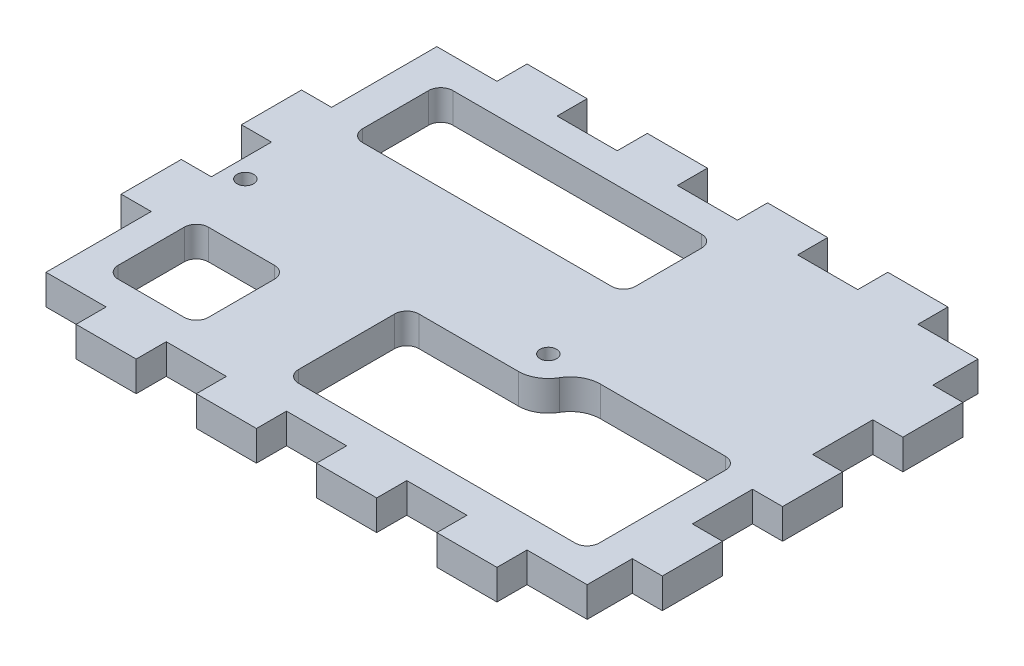
SolidWorks part; units mm, degrees
material "Pine"
ref_plane "Front Plane" through (0, 0, 0) normal (0, 0, 1) x (1, 0, 0)
ref_plane "Top Plane" through (0, 0, 0) normal (0, 1, 0) x (1, 0, 0)
ref_plane "Right Plane" through (0, 0, 0) normal (1, 0, 0) x (0, 0, -1)
sketch "Sketch1" plane through (0, 0, 0) normal (0, 1, 0) x (1, 0, 0)
  line L1 (0, 0) -> (431.8, 0)
  line L2 (0, 0) -> (0, 95.25)
  line L3 (0, 95.25) -> (431.8, 95.25)
  line L4 (431.8, 0) -> (431.8, 95.25)
  dimension "D1" = 431.8
  dimension "D2" = 95.25
extrude "Boss-Extrude1" add sketch "Sketch1" along normal blind 6.35
sketch "Sketch2" plane through (0, 6.35, 0) normal (0, 1, 0) x (1, 0, 0)
  line L1 (431.8, 95.25) -> (0, 95.25) construction
  line L2 (6.35, 95.25) -> (19.05, 95.25)
  line L3 (6.35, 95.25) -> (6.35, 88.9)
  line L4 (6.35, 88.9) -> (19.05, 88.9)
  line L7 (19.05, 95.25) -> (19.05, 88.9)
  line L8 (0, 0) -> (431.8, 0) construction
  line L9 (6.35, 0) -> (19.05, 0)
  line L10 (6.35, 0) -> (6.35, 6.35)
  line L11 (6.35, 6.35) -> (19.05, 6.35)
  line L12 (19.05, 0) -> (19.05, 6.35)
  line L13 (0, 95.25) -> (0, 0) construction
  dimension "D1" = 6.35
  dimension "D2" = 12.7
  dimension "D3" = 6.35
extrude "Cut-Extrude1" cut sketch "Sketch2" against normal through all
pattern_linear "LPattern1" count 17 spacing 25.4 along (1, 0, 0) of "Cut-Extrude1"
sketch "Sketch3" plane through (0, 6.35, 0) normal (0, 1, 0) x (1, 0, 0)
  line L1 (6.35, 88.9) -> (0, 88.9)
  line L2 (6.35, 88.9) -> (6.35, 95.25)
  line L3 (6.35, 95.25) -> (0, 95.25)
  line L4 (0, 88.9) -> (0, 95.25)
  line L5 (6.35, 6.35) -> (0, 6.35)
  line L6 (6.35, 6.35) -> (6.35, 0)
  line L7 (6.35, 0) -> (0, 0)
  line L8 (0, 6.35) -> (0, 0)
  line L9 (425.45, 88.9) -> (431.8, 88.9)
  line L10 (425.45, 88.9) -> (425.45, 95.25)
  line L11 (425.45, 95.25) -> (431.8, 95.25)
  line L12 (431.8, 88.9) -> (431.8, 95.25)
  line L13 (425.45, 6.35) -> (431.8, 6.35)
  line L14 (425.45, 6.35) -> (425.45, 0)
  line L15 (425.45, 0) -> (431.8, 0)
  line L16 (431.8, 6.35) -> (431.8, 0)
extrude "Cut-Extrude2" cut sketch "Sketch3" against normal through all
sketch "Sketch5" plane through (0, 6.35, 0) normal (0, 1, 0) x (1, 0, 0)
  line L0 (311.15, 88.9) -> (311.15, 6.35) construction
  line L1 (190.5, 88.9) -> (190.5, 6.35) construction
  line L2 (184.15, 88.9) -> (196.85, 88.9) construction
  line L3 (196.85, 6.35) -> (184.15, 6.35) construction
  line L5 (190.5, 53.975) -> (184.15, 53.975)
  line L6 (190.5, 53.975) -> (190.5, 41.275)
  line L7 (190.5, 41.275) -> (184.15, 41.275)
  line L8 (184.15, 53.975) -> (184.15, 41.275)
  line L9 (311.15, 53.975) -> (304.8, 53.975)
  line L10 (311.15, 53.975) -> (311.15, 41.275)
  line L11 (311.15, 41.275) -> (304.8, 41.275)
  line L12 (304.8, 53.975) -> (304.8, 41.275)
  point P18 (190.5, 47.625)
  point P19 (311.15, 47.625)
  dimension "D1" = 6.35
  dimension "D2" = 12.7
extrude "Cut-Extrude4" cut sketch "Sketch5" against normal through all
pattern_linear "LPattern2" count 2 spacing 25.4 along (0, 0, -1) count 2 spacing 25.4 along (0, 0, 1) of "Cut-Extrude4"
sketch "Sketch6" plane through (0, 6.35, 0) normal (0, 1, 0) x (1, 0, 0)
  line L0 (190.5, 47.625) -> (304.8, 47.625) construction
  line L1 (190.5, 41.275) -> (190.5, 53.975) construction
  line L2 (304.8, 53.975) -> (304.8, 41.275) construction
  line L4 (304.8, 24.6063) -> (190.5, 24.6062)
  line L5 (304.8, 24.6063) -> (304.8, 70.6438)
  line L6 (304.8, 70.6438) -> (190.5, 70.6437)
  line L7 (190.5, 24.6062) -> (190.5, 70.6437)
  line L8 (304.8, 24.6063) -> (190.5, 70.6437) construction
  line L9 (304.8, 70.6438) -> (190.5, 24.6062) construction
  point P6 (247.65, 47.625)
  dimension "D1" = 46.0375
  dimension "D2" = 114.3
extrude "Cut-Extrude5" cut sketch "Sketch6" against normal through all
sketch "Sketch7" plane through (0, 6.35, 0) normal (0, 1, 0) x (1, 0, 0)
  line L0 (0, 44.45) -> (431.8, 44.45) construction
  line L1 (0, 88.9) -> (0, 6.35) construction
  line L2 (431.8, 6.35) -> (431.8, 88.9) construction
  line L3 (323.85, 0) -> (336.55, 0) construction
  circle A0 centre (52.65, 44.45) radius 1.75
  circle A1 centre (116.65, 44.45) radius 1.75
  circle A2 centre (315.15, 44.45) radius 1.75
  circle A3 centre (379.15, 44.45) radius 1.75
  dimension "D6" = 3.5
  dimension "D1" = 44.45
  dimension "D2" = 64
  dimension "D3" = 64
  dimension "D4" = 116.65
  dimension "D5" = 116.65
extrude "Cut-Extrude6" cut sketch "Sketch7" against normal through all
sketch "Sketch8" plane through (0, 6.35, 0) normal (0, 1, 0) x (1, 0, 0)
  line L0 (0, 88.9) -> (0, 6.35) construction
  line L1 (0, 88.9) -> (6.35, 88.9)
  line L2 (0, 88.9) -> (0, 79.375)
  line L3 (0, 79.375) -> (6.35, 79.375)
  line L4 (6.35, 88.9) -> (6.35, 79.375)
  line L5 (0, 6.35) -> (6.35, 6.35)
  line L6 (0, 6.35) -> (0, 15.875)
  line L7 (0, 15.875) -> (6.35, 15.875)
  line L8 (6.35, 6.35) -> (6.35, 15.875)
  line L9 (0, 28.575) -> (6.35, 28.575)
  line L10 (0, 28.575) -> (0, 41.275)
  line L11 (0, 41.275) -> (6.35, 41.275)
  line L12 (6.35, 28.575) -> (6.35, 41.275)
  line L13 (190.5, 53.975) -> (184.15, 53.975) construction
  line L14 (0, 66.675) -> (6.35, 66.675)
  line L15 (0, 66.675) -> (0, 53.975)
  line L16 (0, 53.975) -> (6.35, 53.975)
  line L17 (6.35, 66.675) -> (6.35, 53.975)
  line L18 (184.15, 41.275) -> (190.5, 41.275) construction
  line L19 (190.5, 28.575) -> (184.15, 28.575) construction
  line L20 (19.05, 0) -> (19.05, 6.35) construction
  line L21 (190.5, 79.375) -> (184.15, 79.375) construction
  line L22 (184.15, 15.875) -> (190.5, 15.875) construction
extrude "Cut-Extrude7" cut sketch "Sketch8" against normal through all
pattern_linear "LPattern3" count 2 spacing 425.45 along (1, 0, 0) of "Cut-Extrude7"
sketch "Sketch9" plane through (0, 6.35, 0) normal (0, 1, 0) x (1, 0, 0)
  line L0 (311.15, 95.25) -> (298.45, 95.25) construction
  line L1 (304.8, 95.25) -> (0, 95.25)
  line L2 (304.8, 95.25) -> (304.8, 0)
  line L3 (304.8, 0) -> (0, 0)
  line L4 (0, 95.25) -> (0, 0)
extrude "Cut-Extrude8" cut sketch "Sketch9" against normal through all
sketch "Sketch10" plane through (0, 6.35, 0) normal (0, 1, 0) x (1, 0, 0)
  line L1 (311.15, 95.25) -> (304.8, 95.25)
  line L2 (311.15, 95.25) -> (311.15, 79.375)
  line L3 (311.15, 79.375) -> (304.8, 79.375)
  line L4 (304.8, 95.25) -> (304.8, 79.375)
  line L5 (304.8, 15.875) -> (311.15, 15.875)
  line L6 (304.8, 15.875) -> (304.8, 0)
  line L7 (304.8, 0) -> (311.15, 0)
  line L8 (311.15, 15.875) -> (311.15, 0)
extrude "Cut-Extrude9" cut sketch "Sketch10" against normal through all
sketch "Sketch11" plane through (0, 6.35, 0) normal (0, 1, 0) x (1, 0, 0)
  line L0 (361.95, 88.9) -> (374.65, 88.9) construction
  line L1 (318.325, 63.5) -> (375.975, 63.5)
  line L2 (318.325, 63.5) -> (318.325, 82.55)
  line L3 (318.325, 82.55) -> (375.975, 82.55)
  line L4 (375.975, 63.5) -> (375.975, 82.55)
  circle A0 centre (315.15, 44.45) radius 1.75 construction
  circle A1 centre (379.15, 44.45) radius 1.75 construction
  dimension "D1" = 3.175
  dimension "D2" = 3.175
  dimension "D3" = 6.35
  dimension "D4" = 19.05
extrude "Cut-Extrude10" cut sketch "Sketch11" against normal through all
sketch "Sketch12" plane through (0, 6.35, 0) normal (0, 1, 0) x (1, 0, 0)
  line L0 (374.65, 6.35) -> (361.95, 6.35) construction
  line L1 (419.1, 38.1) -> (355.6, 38.1)
  line L2 (419.1, 38.1) -> (419.1, 12.7)
  line L3 (419.1, 12.7) -> (355.6, 12.7)
  line L4 (355.6, 38.1) -> (355.6, 12.7)
  line L5 (425.45, 41.275) -> (425.45, 28.575) construction
  dimension "D1" = 31.75
  dimension "D2" = 25.4
  dimension "D3" = 6.35
  dimension "D4" = 63.5
extrude "Cut-Extrude11" cut sketch "Sketch12" against normal through all
sketch "Sketch13" plane through (0, 6.35, 0) normal (0, 1, 0) x (1, 0, 0)
  line L0 (311.15, 6.35) -> (311.15, 28.575) construction
  line L1 (317.5, 31.75) -> (336.55, 31.75)
  line L2 (317.5, 31.75) -> (317.5, 12.7)
  line L3 (317.5, 12.7) -> (336.55, 12.7)
  line L4 (336.55, 31.75) -> (336.55, 12.7)
  line L5 (323.85, 6.35) -> (311.15, 6.35) construction
  dimension "D1" = 6.35
  dimension "D2" = 6.35
  dimension "D3" = 19.05
  dimension "D4" = 19.05
extrude "Cut-Extrude12" cut sketch "Sketch13" against normal through all
sketch "Sketch14" plane through (0, 6.35, 0) normal (0, 1, 0) x (1, 0, 0)
  line L1 (419.1, 38.1) -> (385.5, 38.1)
  line L2 (419.1, 38.1) -> (419.1, 44.45)
  line L3 (419.1, 44.45) -> (385.5, 44.45)
  line L4 (385.5, 38.1) -> (385.5, 44.45)
  circle A0 centre (379.15, 44.45) radius 1.75 construction
  dimension "D2" = 6.35
  dimension "D1" = 6.35
extrude "Cut-Extrude13" cut sketch "Sketch14" against normal through all
fillet "Fillet1" radius 6.35 1 edges at (385.5, 3.175, -38.1)
fillet "Fillet2" radius 6.35 1 edges at (385.5, 3.175, -44.45)
fillet "Fillet3" radius 2.54 12 edges at (355.6, 3.175, -12.7) (336.55, 3.175, -12.7) (336.55, 3.175, -31.75) (317.5, 3.175, -31.75) (355.6, 3.175, -38.1) (419.1, 3.175, -44.45) (317.5, 3.175, -12.7) (318.325, 3.175, -63.5) (419.1, 3.175, -12.7) (375.975, 3.175, -63.5) (375.975, 3.175, -82.55) (318.325, 3.175, -82.55)
